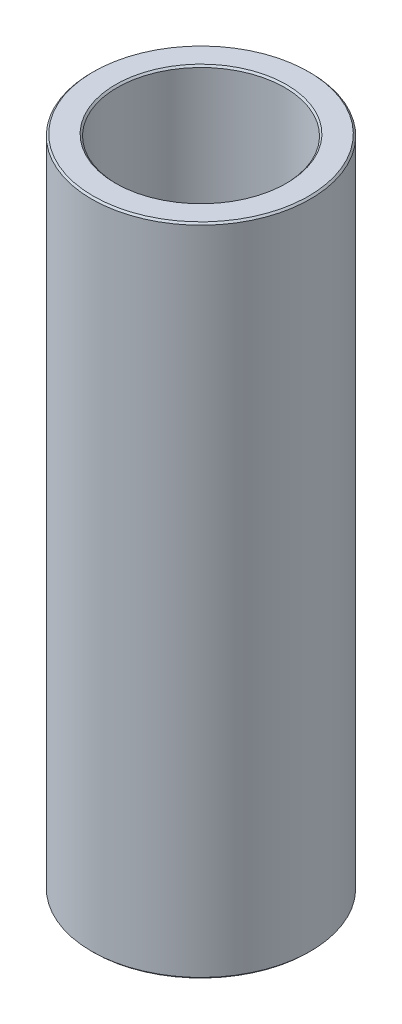
SolidWorks part; units mm, degrees
ref_plane "Front Plane" through (0, 0, 0) normal (0, 0, 1) x (1, 0, 0)
ref_plane "Top Plane" through (0, 0, 0) normal (0, 1, 0) x (1, 0, 0)
ref_plane "Right Plane" through (0, 0, 0) normal (1, 0, 0) x (0, 0, -1)
sketch "Sketch1" plane through (0, 0, 0) normal (0, 1, 0) x (1, 0, 0)
  circle A0 centre (0, 0) radius 20
  dimension "SLEEVE_OD" = 40
extrude "Boss-Extrude1" add sketch "Sketch1" along normal blind 119.7044
sketch "Sketch2" plane through (0, 0, 0) normal (0, 1, 0) x (1, 0, 0)
  circle A0 centre (0, 0) radius 15.3215
  dimension "BORE_D" = 30.6429
extrude "Cut-Extrude1" cut sketch "Sketch2" along normal through all
chamfer "Chamfer1" distance 0.3117 angle 45 4 edges at (0, 119.7044, 15.3215) (0, 0, 15.3215) (0, 0, 20) (0, 119.7044, 20)
